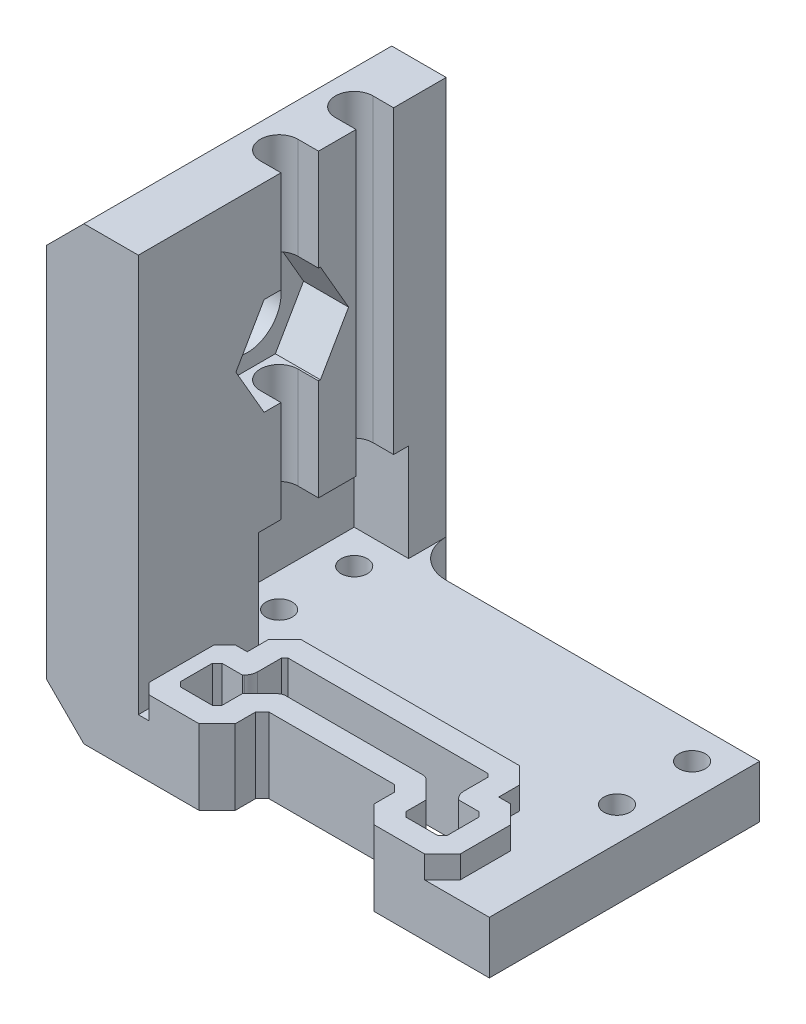
SolidWorks part; units mm, degrees
ref_plane "Front Plane" through (0, 0, 0) normal (0, 0, 1) x (1, 0, 0)
ref_plane "Top Plane" through (0, 0, 0) normal (0, 1, 0) x (1, 0, 0)
ref_plane "Right Plane" through (0, 0, 0) normal (1, 0, 0) x (0, 0, -1)
ref_plane "Plane1" through (0, 200, 0) normal (0, 1, 0) x (1, 0, 0)
sketch "Sketch1" plane through (0, 200, 0) normal (0, 1, 0) x (1, 0, 0)
  line L0 (0, -3.8557) -> (0.25, -4)
  line L1 (0.25, -4) -> (9.0787, -4)
  line L2 (10.1394, -4.4394) -> (12.5, -6.8)
  line L3 (12.5, -6.8) -> (12.5, -9.5)
  line L4 (12.5, -9.5) -> (13, -10)
  line L5 (13, -10) -> (17, -10)
  line L6 (17, -10) -> (17.5, -9.5)
  line L7 (17.5, -9.5) -> (17.5, -5.5)
  line L8 (17.5, -5.5) -> (17, -5)
  line L9 (17, -5) -> (14.3, -5)
  line L10 (14.3, -5) -> (14.0858, -4.7858)
  line L11 (13.5, -3.3716) -> (13.5, -0.3)
  line L12 (13.5, -0.3) -> (13.2, 0)
  line L13 (13.2, 0) -> (7.5, 0)
  line L14 (7.5, 0) -> (7.4, -0.1)
  line L15 (7.4, -0.1) -> (-7.4, -0.1)
  line L16 (-7.4, -0.1) -> (-7.5, 0)
  line L17 (-7.5, 0) -> (-13.2, 0)
  line L18 (-13.2, 0) -> (-13.5, -0.3)
  line L19 (-13.5, -0.3) -> (-13.5, -3.3716)
  line L20 (-14.0858, -4.7858) -> (-14.3, -5)
  line L21 (-14.3, -5) -> (-17, -5)
  line L22 (-17, -5) -> (-17.5, -5.5)
  line L23 (-17.5, -5.5) -> (-17.5, -9.5)
  line L24 (-17.5, -9.5) -> (-17, -10)
  line L25 (-17, -10) -> (-13, -10)
  line L26 (-13, -10) -> (-12.5, -9.5)
  line L27 (-12.5, -9.5) -> (-12.5, -6.8)
  line L28 (-12.5, -6.8) -> (-10.1394, -4.4394)
  line L29 (-9.0787, -4) -> (-0.25, -4)
  line L30 (-0.25, -4) -> (0, -3.8557)
  arc A0 (9.0787, -4) -> (10.1394, -4.4394) centre (9.0787, -5.5) cw
  arc A1 (14.0858, -4.7858) -> (13.5, -3.3716) centre (15.5, -3.3716) cw
  arc A2 (-13.5, -3.3716) -> (-14.0858, -4.7858) centre (-15.5, -3.3716) cw
  arc A3 (-10.1394, -4.4394) -> (-9.0787, -4) centre (-9.0787, -5.5) cw
extrude "Boss-Extrude1" add sketch "Sketch1" against normal blind 400
ref_plane "Plane2" through (0, 210, 0) normal (0, 1, 0) x (1, 0, 0)
sketch "Sketch2" plane through (0, 210, 0) normal (0, 1, 0) x (1, 0, 0)
  line L0 (-8.3538, -7.25) -> (8.3538, -7.25)
  line L1 (8.3538, -7.25) -> (9.25, -8.1462)
  line L2 (13.3036, 0.25) -> (-13.3036, 0.25)
  line L3 (-13.3036, 0.25) -> (-13.75, -0.1965)
  line L4 (-13.75, -0.1965) -> (-13.75, -3.3716)
  line L5 (-14.2626, -4.609) -> (-14.4036, -4.75)
  line L6 (-14.4036, -4.75) -> (-17.1036, -4.75)
  line L7 (-17.1036, -4.75) -> (-17.75, -5.3965)
  line L8 (-17.75, -5.3965) -> (-17.75, -9.6036)
  line L9 (-17.75, -9.6036) -> (-17.1036, -10.25)
  line L10 (-17.1036, -10.25) -> (-12.8965, -10.25)
  line L11 (-12.8965, -10.25) -> (-12.25, -9.6036)
  line L12 (-12.25, -9.6036) -> (-12.25, -6.9036)
  line L13 (-12.25, -6.9036) -> (-9.9626, -4.6162)
  line L14 (-9.0787, -4.25) -> (9.0787, -4.25)
  line L15 (9.9626, -4.6162) -> (12.25, -6.9036)
  line L16 (12.25, -6.9036) -> (12.25, -9.6036)
  line L17 (12.25, -9.6036) -> (12.8965, -10.25)
  line L18 (12.8965, -10.25) -> (17.1036, -10.25)
  line L19 (17.1036, -10.25) -> (17.75, -9.6036)
  line L20 (17.75, -9.6036) -> (17.75, -5.3965)
  line L21 (17.75, -5.3965) -> (17.1036, -4.75)
  line L22 (17.1036, -4.75) -> (14.4036, -4.75)
  line L23 (14.4036, -4.75) -> (14.2626, -4.609)
  line L24 (13.75, -3.3716) -> (13.75, -0.1965)
  line L25 (13.75, -0.1965) -> (13.3036, 0.25)
  line L26 (9.25, -8.1462) -> (9.25, -10.8462)
  line L27 (9.25, -10.8462) -> (11.6538, -13.25)
  line L28 (11.6538, -13.25) -> (18.3462, -13.25)
  line L29 (18.3462, -13.25) -> (20.75, -10.8462)
  line L30 (20.75, -10.8462) -> (20.75, -4.1538)
  line L31 (20.75, -4.1538) -> (18.3462, -1.75)
  line L32 (18.3462, -1.75) -> (16.75, -1.75)
  line L33 (16.75, -1.75) -> (16.75, -1.75)
  line L34 (16.75, -1.75) -> (16.75, 1.0462)
  line L35 (16.75, 1.0462) -> (14.5462, 3.25)
  line L36 (14.5462, 3.25) -> (-14.5462, 3.25)
  line L37 (-14.5462, 3.25) -> (-16.75, 1.0462)
  line L38 (-16.75, 1.0462) -> (-16.75, -1.75)
  line L39 (-16.75, -1.75) -> (-16.75, -1.75)
  line L40 (-16.75, -1.75) -> (-18.3462, -1.75)
  line L41 (-18.3462, -1.75) -> (-20.75, -4.1538)
  line L42 (-20.75, -4.1538) -> (-20.75, -10.8462)
  line L43 (-20.75, -10.8462) -> (-18.3462, -13.25)
  line L44 (-18.3462, -13.25) -> (-11.6538, -13.25)
  line L45 (-11.6538, -13.25) -> (-9.25, -10.8462)
  line L46 (-9.25, -10.8462) -> (-9.25, -8.1462)
  line L47 (-9.25, -8.1462) -> (-8.3538, -7.25)
  arc A0 (-14.2626, -4.609) -> (-13.75, -3.3716) centre (-15.5, -3.3716) ccw
  arc A1 (-9.0787, -4.25) -> (-9.9626, -4.6162) centre (-9.0787, -5.5) ccw
  arc A2 (9.9626, -4.6162) -> (9.0787, -4.25) centre (9.0787, -5.5) ccw
  arc A3 (13.75, -3.3716) -> (14.2626, -4.609) centre (15.5, -3.3716) ccw
  arc A4 (8.3538, -7.25) -> (8.3538, -7.25) centre (8.3538, -7.25) ccw
  arc A5 (16.75, -1.75) -> (16.75, -1.75) centre (16.75, -1.75) ccw
  arc A6 (-16.75, -1.75) -> (-16.75, -1.75) centre (-16.75, -1.75) ccw
  arc A7 (-8.3538, -7.25) -> (-8.3538, -7.25) centre (-8.3538, -7.25) ccw
  dimension "D1" = 3
extrude "Boss-Extrude2" add sketch "Sketch2" along normal blind 10 separate body
sketch "Sketch3" plane through (0, 200, 0) normal (0, 1, 0) x (1, 0, 0)
  line L0 (7.4, -0.1) -> (-7.4, -0.1) construction
  circle A0 centre (0, -0.1) radius 43.001
extrude "Cut-Extrude1" cut sketch "Sketch3" against normal blind 447.3602
sketch "Sketch4" plane through (0, 210, 0) normal (0, -1, 0) x (-1, 0, 0)
  line L0 (-13.3036, 0.25) -> (13.3036, 0.25) construction
  line L1 (27, 22.75) -> (-27, 22.75)
  line L2 (27, 22.75) -> (27, -13.25)
  line L3 (27, -13.25) -> (18.3462, -13.25)
  line L4 (-27, 22.75) -> (-27, -13.25)
  line L5 (-27, -13.25) -> (-18.3462, -13.25)
  line L25 (8.3538, -7.25) -> (9.25, -8.1462)
  line L26 (9.25, -8.1462) -> (9.25, -10.8462)
  line L27 (9.25, -10.8462) -> (11.6538, -13.25)
  line L28 (11.6538, -13.25) -> (18.3462, -13.25)
  line L29 (18.3462, -13.25) -> (20.75, -10.8462)
  line L30 (20.75, -10.8462) -> (20.75, -4.1538)
  line L31 (20.75, -4.1538) -> (18.3462, -1.75)
  line L32 (18.3462, -1.75) -> (16.75, -1.75)
  line L33 (16.75, -1.75) -> (16.75, 1.0462)
  line L34 (16.75, 1.0462) -> (14.5462, 3.25)
  line L35 (14.5462, 3.25) -> (-14.5462, 3.25)
  line L36 (-14.5462, 3.25) -> (-16.75, 1.0462)
  line L37 (-16.75, 1.0462) -> (-16.75, -1.75)
  line L38 (-16.75, -1.75) -> (-18.3462, -1.75)
  line L39 (-18.3462, -1.75) -> (-20.75, -4.1538)
  line L40 (-20.75, -4.1538) -> (-20.75, -10.8462)
  line L41 (-20.75, -10.8462) -> (-18.3462, -13.25)
  line L42 (-18.3462, -13.25) -> (-11.6538, -13.25)
  line L43 (-11.6538, -13.25) -> (-9.25, -10.8462)
  line L44 (-9.25, -10.8462) -> (-9.25, -8.1462)
  line L45 (-9.25, -8.1462) -> (-8.3538, -7.25)
  line L46 (-8.3538, -7.25) -> (8.3538, -7.25)
  line L47 (8.3538, -7.25) -> (9.25, -8.1462)
  line L48 (9.25, -8.1462) -> (9.25, -10.8462)
  line L49 (9.25, -10.8462) -> (11.6538, -13.25)
  line L50 (11.6538, -13.25) -> (18.3462, -13.25)
  line L51 (18.3462, -13.25) -> (20.75, -10.8462)
  line L52 (20.75, -10.8462) -> (20.75, -4.1538)
  line L53 (20.75, -4.1538) -> (18.3462, -1.75)
  line L54 (18.3462, -1.75) -> (16.75, -1.75)
  line L55 (16.75, -1.75) -> (16.75, 1.0462)
  line L56 (16.75, 1.0462) -> (14.5462, 3.25)
  line L57 (14.5462, 3.25) -> (-14.5462, 3.25)
  line L58 (-14.5462, 3.25) -> (-16.75, 1.0462)
  line L59 (-16.75, 1.0462) -> (-16.75, -1.75)
  line L60 (-16.75, -1.75) -> (-18.3462, -1.75)
  line L61 (-18.3462, -1.75) -> (-20.75, -4.1538)
  line L62 (-20.75, -4.1538) -> (-20.75, -10.8462)
  line L63 (-20.75, -10.8462) -> (-18.3462, -13.25)
  line L64 (-18.3462, -13.25) -> (-11.6538, -13.25)
  line L65 (-11.6538, -13.25) -> (-9.25, -10.8462)
  line L66 (-9.25, -10.8462) -> (-9.25, -8.1462)
  line L67 (-9.25, -8.1462) -> (-8.3538, -7.25)
  line L68 (-8.3538, -7.25) -> (8.3538, -7.25)
  point P8 (0, 22.75)
  point P29 (0, 0.25)
  line M32 (20.75, -4.1538) -> (18.3462, -1.75)
  line M33 (18.3462, -1.75) -> (16.75, -1.75)
  line M34 (16.75, -1.75) -> (16.75, 1.0462)
  line M35 (16.75, 1.0462) -> (14.5462, 3.25)
  line M36 (14.5462, 3.25) -> (-14.5462, 3.25)
  line M37 (-14.5462, 3.25) -> (-16.75, 1.0462)
  line M38 (-16.75, 1.0462) -> (-16.75, -1.75)
  line M39 (-16.75, -1.75) -> (-18.3462, -1.75)
  line M40 (-18.3462, -1.75) -> (-20.75, -4.1538)
  dimension "D2" = 19.5
  dimension "D3" = 54
  dimension "D4" = 0
  dimension "D1" = 0
extrude "Boss-Extrude3" add sketch "Sketch4" against normal blind 7 contours L1 M40 M39 M38 M37 M36 M35 M34 M33 M32 region at (0, 210, -9.587)
sketch "Sketch5" plane through (0, 210, 0) normal (0, -1, 0) x (-1, 0, 0)
  line L0 (0, 22.75) -> (0, 9.6848) construction
  line L1 (27, 22.75) -> (-27, 22.75) construction
  line L2 (27, 22.75) -> (27, -13.25) construction
  circle A0 centre (22.5, 18.25) radius 1.75
  circle A1 centre (22.5, 8.25) radius 1.75
  circle A2 centre (-22.5, 8.25) radius 1.75
  circle A3 centre (-22.5, 18.25) radius 1.75
  dimension "D4" = 3.5
  dimension "D1" = 10
  dimension "D2" = 4.5
  dimension "D3" = 4.5
extrude "Cut-Extrude2" cut sketch "Sketch5" against normal blind 33
sketch "Sketch6" plane through (-27, 0, 0) normal (-1, 0, 0) x (0, 0, 1)
  line L1 (-22.75, 210) -> (13.25, 210)
  line L2 (-22.75, 210) -> (-22.75, 270)
  line L3 (-22.75, 270) -> (13.25, 270)
  line L4 (13.25, 210) -> (13.25, 270)
  dimension "D1" = 60
extrude "Boss-Extrude4" add sketch "Sketch6" along normal blind 5
sketch "Sketch7" plane through (0, 217, 0) normal (0, 1, 0) x (1, 0, 0)
  line L0 (-20.75, -10.8462) -> (-20.75, -4.1538) construction
  line L1 (-27, -13.25) -> (-19.75, -13.25)
  line L2 (-27, -13.25) -> (-27, 2.75)
  line L3 (-27, 2.75) -> (-19.75, 2.75)
  line L4 (-19.75, -13.25) -> (-19.75, 2.75)
  dimension "D1" = 1
  dimension "D2" = 16
extrude "Boss-Extrude5" add sketch "Sketch7" along normal up to surface (53 mm away) up to face at (-29.5, 270, -4.75)
sketch "Sketch8" plane through (0, 0, -22.75) normal (0, 0, -1) x (-1, 0, 0)
  line L0 (32, 210) -> (-27, 210) construction
  line L1 (32, 270) -> (19.75, 270)
  line L2 (32, 270) -> (32, 210)
  line L3 (32, 210) -> (19.75, 210)
  line L4 (19.75, 270) -> (19.75, 210)
  dimension "D1" = 0
extrude "Boss-Extrude6" add sketch "Sketch8" along normal blind 5
fillet "Fillet1" radius 5 1 edges at (-19.75, 213.5, -22.75)
sketch "Sketch10" plane through (-27, 0, 0) normal (1, 0, 0) x (0, 0, -1)
  line L0 (22.75, 270) -> (22.75, 217) construction
  line L1 (2.75, 270) -> (22.75, 270)
  line L2 (2.75, 270) -> (2.75, 230)
  line L3 (2.75, 230) -> (22.75, 230)
  line L4 (22.75, 270) -> (22.75, 230)
  dimension "D1" = 40
extrude "Boss-Extrude7" add sketch "Sketch10" along normal up to surface (7.25 mm away) up to face at (-19.75, 231, 6.375)
sketch "Sketch9" plane through (-19.75, 0, 0) normal (1, 0, 0) x (0, 0, -1)
  line L0 (-13.25, 250) -> (27.75, 250) construction
  line L1 (14.7555, 250) -> (11.0027, 256.5)
  line L2 (11.0027, 256.5) -> (3.4972, 256.5)
  line L3 (3.4972, 256.5) -> (-0.2556, 250)
  line L4 (-0.2556, 250) -> (3.4972, 243.5)
  line L5 (3.4972, 243.5) -> (11.0027, 243.5)
  line L6 (11.0027, 243.5) -> (14.7555, 250)
  line L8 (-13.25, 270) -> (-13.25, 217) construction
  line L9 (27.75, 270) -> (27.75, 217) construction
  line L10 (27.75, 270) -> (-13.25, 270) construction
  circle A0 centre (7.25, 250) radius 6.5 construction
  dimension "D1" = 13
  dimension "D2" = 20
extrude "Cut-Extrude3" cut sketch "Sketch9" against normal blind 6
sketch "Sketch11" plane through (0, 217, 0) normal (0, 1, 0) x (1, 0, 0)
  line L0 (-22.5, 20.75) -> (-17.8248, 20.75)
  line L1 (-17.8248, 20.75) -> (-17.8248, 15.75)
  line L2 (-17.8248, 15.75) -> (-22.5, 15.75)
  line L3 (-22.5, 10.75) -> (-17.8248, 10.75)
  line L4 (-17.8248, 10.75) -> (-17.8248, 5.75)
  line L5 (-17.8248, 5.75) -> (-22.5, 5.75)
  arc A0 (-22.5, 20.75) -> (-22.5, 15.75) centre (-22.5, 18.25) ccw
  arc A1 (-22.5, 10.75) -> (-22.5, 5.75) centre (-22.5, 8.25) ccw
  dimension "D1" = 5
  dimension "D2" = 5
extrude "Cut-Extrude4" cut sketch "Sketch11" along normal through all
sketch "Sketch12" plane through (-25.75, 0, 0) normal (1, 0, 0) x (0, 0, -1)
  line L0 (14.7555, 250) -> (-0.2556, 250) construction
  circle A0 centre (7.25, 250) radius 4.5
  dimension "D1" = 9
extrude "Cut-Extrude5" cut sketch "Sketch12" against normal blind 16
chamfer "Chamfer2" distance 5 angle 45 1 edges at (-32, 270, -7.25)
chamfer "Chamfer3" distance 5 angle 45 1 edges at (-32, 210, -7.25)
sketch "Sketch13" plane through (-32, 0, 0) normal (-1, 0, 0) x (0, 0, 1)
  circle A0 centre (-7.25, 250) radius 4.5
  circle A1 centre (-7.25, 250) radius 6.5
  dimension "D1" = 2
extrude "Boss-Extrude8" add sketch "Sketch13" along normal blind 1
fillet "Fillet2" radius 1 1 edges at (-32, 250, -13.75)
